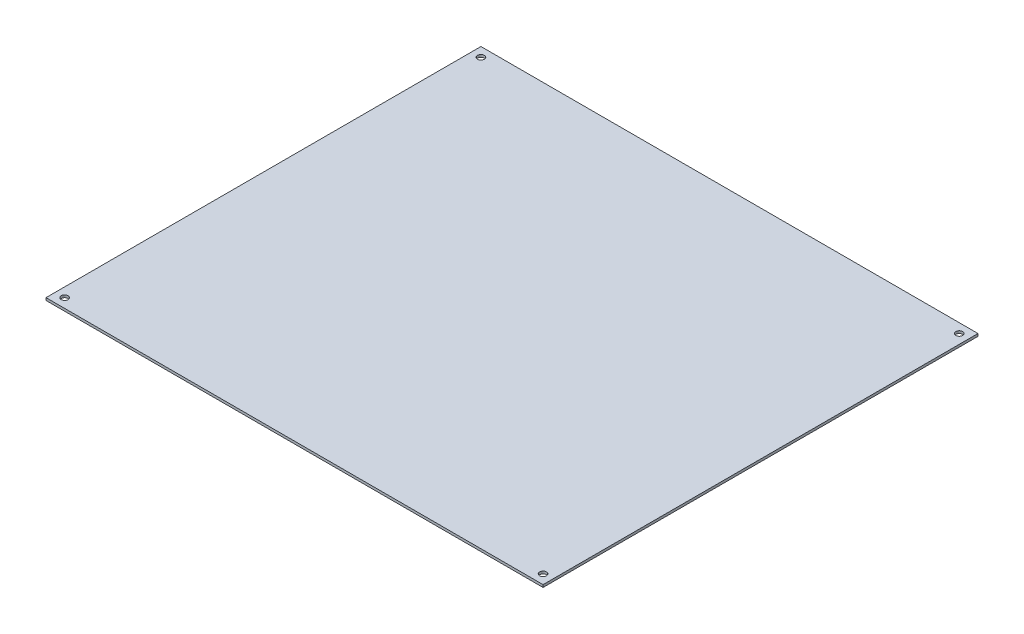
SolidWorks part; units mm, degrees
ref_plane "Front Plane" through (0, 0, 0) normal (0, 0, 1) x (1, 0, 0)
ref_plane "Top Plane" through (0, 0, 0) normal (0, 1, 0) x (1, 0, 0)
ref_plane "Right Plane" through (0, 0, 0) normal (1, 0, 0) x (0, 0, -1)
sketch "Sketch1" plane through (0, 0, 0) normal (0, 1, 0) x (1, 0, 0)
  line L0 (80, 0) -> (80, -12.9) construction
  line L1 (0, 0) -> (160, 0)
  line L2 (0, 0) -> (0, 140)
  line L3 (0, 140) -> (160, 140)
  line L4 (160, 0) -> (160, 140)
  line L5 (0, 70) -> (-11.7211, 70) construction
  circle A0 centre (3, 3) radius 1.1
  circle A2 centre (3, 137) radius 1.1
  circle A3 centre (157, 137) radius 1.1
  circle A4 centre (157, 3) radius 1.1
  point P9 (80, 0)
  point P10 (0, 70)
  dimension "D3" = 67
  dimension "D5" = 2.2
  dimension "D1" = 140
  dimension "D2" = 160
  dimension "D6" = 77
extrude "Boss-Extrude1" add sketch "Sketch1" along normal blind 0.8
sketch "Sketch2" plane through (0, 0.8, 0) normal (0, 1, 0) x (1, 0, 0)
  line L0 (111.3333, 292) -> (556.6667, 292) construction
